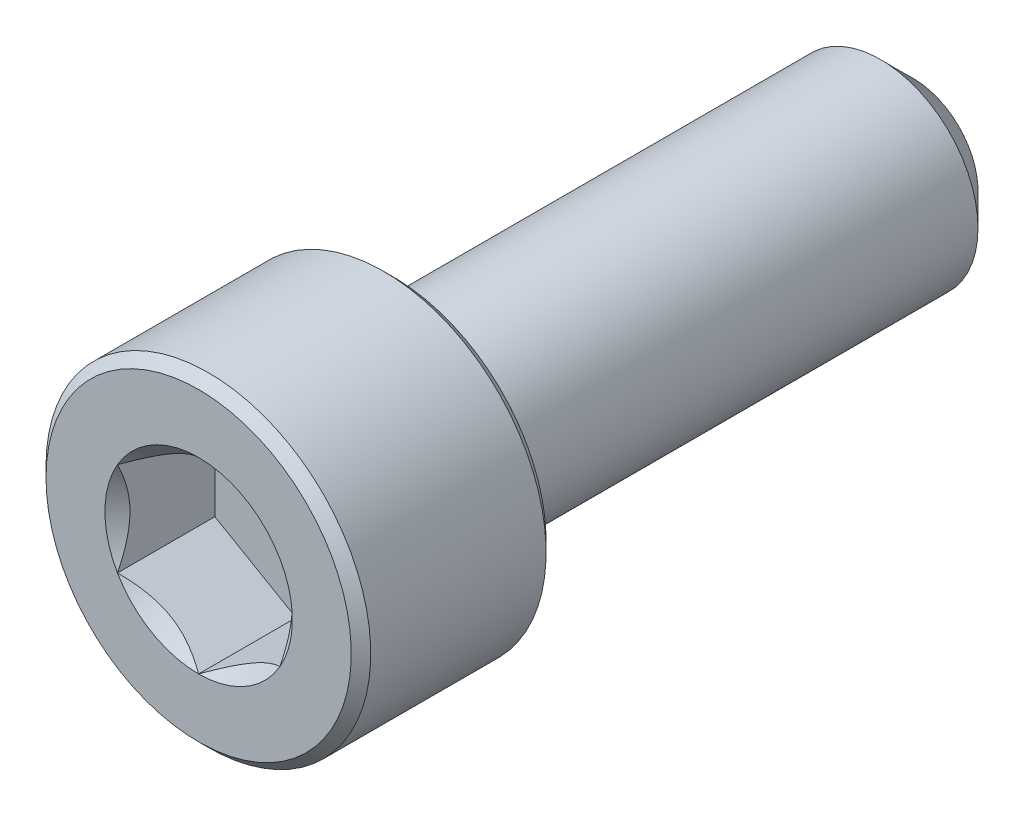
SolidWorks part; units mm, degrees
ref_plane "Front Plane" through (0, 0, 0) normal (0, 0, 1) x (1, 0, 0)
ref_plane "Top Plane" through (0, 0, 0) normal (0, 1, 0) x (1, 0, 0)
ref_plane "Right Plane" through (0, 0, 0) normal (1, 0, 0) x (0, 0, -1)
sketch "Sketch1" plane through (0, 0, 0) normal (1, 0, 0) x (0, 0, -1)
  line L0 (-11, 0) -> (11, 0) construction
  line L1 (11, 0) -> (11, 2) construction
  line L2 (11, 2) -> (10, 3) construction
  line L3 (10, 3) -> (-5, 3) construction
  line L5 (-5, 3) -> (-5, 5) construction
  line L6 (-5, 5) -> (-11, 5) construction
  line L7 (-11, 5) -> (-11, 0) construction
  line L8 (11, 2) -> (11, 3) construction
  line L9 (10.9375, 3.1083) -> (11.4375, 2.2422) construction
  line L10 (11.4375, 2.2422) -> (11.9375, 3.1083) construction
  line L11 (11.9375, 3.1083) -> (10.9375, 3.1083) construction
  line L12 (11.4375, 3.1083) -> (11.4375, 3) construction
  line L13 (11.4375, 2.2422) -> (11.4375, 2.3505) construction
  line L14 (11.375, 2.3505) -> (11.5, 2.3505) construction
  line L15 (11, 3) -> (11.875, 3) construction
  line L16 (10.9687, 3.0541) -> (11.9062, 3.0541) construction
  line L17 (11, 0) -> (11, -3) construction
  line L18 (-5.3, 5) -> (-5, 4.7) construction
  line L19 (-10.7, 5) -> (-11, 4.7) construction
  point P0 (-11, 2.5)
  point P3 (7.5, 3)
  point P4 (0, 0)
  point P22 (11.4375, 2.3505)
  point P24 (-5, 3)
  point P25 (11.4375, 3)
  point P28 (11.4375, 3.0541)
  point P29 (7.5, -3)
  point P31 (-8, 5)
  point P37 (-6.05, 5)
  point P38 (-10.55, 5)
  point P41 (-8, 0)
  dimension "head height" = 6
  dimension "D1" = 45
  dimension "Head Diameter" = 10
  dimension "Thread Size" = 6
  dimension "drive size" = 5
  dimension "Thread Pitch" = 1
  dimension "D2" = 0.125
  dimension "D3" = 1
  dimension "D4" = 3.5
  dimension "D7" = 0.3
  dimension "D8" = 0.3
  dimension "D9" = 0.3
  dimension "D10" = 0.15
  dimension "D11" = 0.75
  dimension "length" = 16
  dimension "Drive Depth" = 3
sketch "Sketch2" plane through (0, 0, 0) normal (1, 0, 0) x (0, 0, -1)
  line L1 (-10.7, 5) -> (-5.3, 5)
  line L4 (10, 3) -> (11, 2)
  line L5 (11, 2) -> (11, 0)
  line L6 (-5.3, 5) -> (-5, 4.7) construction
  line L7 (11, 0) -> (-11, 0)
  line L8 (-10.7, 5) -> (-11, 4.7) construction
  line L9 (-5.3, 5) -> (-5, 4.7)
  line L10 (-10.7, 5) -> (-11, 4.7)
  line L11 (-11, 4.7) -> (-11, 0)
  line L12 (-5, 4.7) -> (-5, 3)
  line L13 (-5, 3) -> (10, 3)
revolve "Revolve1" add sketch "Sketch2" angle 360 about L7
sketch "Sketch3" plane through (0, 0, 11) normal (0, 0, 1) x (1, 0, 0)
  line L1 (0, 2.8868) -> (-2.5, 1.4434)
  line L2 (-2.5, 1.4434) -> (-2.5, -1.4434)
  line L3 (-2.5, -1.4434) -> (0, -2.8868)
  line L4 (0, -2.8868) -> (2.5, -1.4434)
  line L5 (2.5, -1.4434) -> (2.5, 1.4434)
  line L6 (2.5, 1.4434) -> (0, 2.8868)
  circle A0 centre (0, 0) radius 2.5 construction
  dimension "D1" = 5
extrude "Cut-Extrude1" cut sketch "Sketch3" against normal up to vertex (3 mm away) up to point (0, 0, 8)
sketch "Sketch4" plane through (0, 0, 11) normal (0, 0, 1) x (1, 0, 0)
  circle A0 centre (0, 0) radius 2.8868
extrude "Cut-Extrude2" cut sketch "Sketch4" against normal blind 0.5 draft 45
ref_plane "Plane1" [suppressed] through (0, 0, 5) normal (0, 0, 1) x (1, 0, 0)
split "Split1" [suppressed] bodies to split 106
sketch "Sketch6" [suppressed] plane through (0, 0, -11) normal (0, 0, -1) x (-1, 0, 0)
  circle A0 centre (0, 0) radius 3
curve "Helix/Spiral1" [suppressed] pitch 1 height 17 turns 17
sketch "Sketch7" [suppressed] plane through (0, 0, 0) normal (1, 0, 0) x (0, 0, -1)
  line L0 (10.9687, 3.0541) -> (11.9062, 3.0541)
  line L1 (11.9062, 3.0541) -> (11.5, 2.3505)
  line L2 (11.5, 2.3505) -> (11.375, 2.3505)
  line L3 (11.375, 2.3505) -> (10.9687, 3.0541)
sweep "Cut-Sweep1" [suppressed] cut profiles "Sketch7" path "Helix/Spiral1"
sketch "Sketch8" [suppressed] plane through (0, 0, 5) normal (0, 0, -1) x (-1, 0, 0)
  circle A0 centre (0, 0) radius 3
extrude "Boss-Extrude1" [suppressed] add sketch "Sketch8" along normal through all draft 45
ref_plane "Plane2" [suppressed] through (0, 0, 8) normal (0, 0, 1) x (1, 0, 0)
sketch "Sketch9" [suppressed] plane through (0, 0, 8) normal (0, 0, 1) x (1, 0, 0)
  line L0 (0, 4.8625) -> (0.1309, 4.9983)
  line L1 (0, 4.8625) -> (-0.1309, 4.9983)
  line L2 (0, 5) -> (0, 0) construction
  line L3 (-0.1309, 4.9983) -> (0, 0) construction
  line L4 (0, 0) -> (0.1309, 4.9983) construction
  arc A0 (0.1309, 4.9983) -> (-0.1309, 4.9983) centre (0, 0) ccw
  circle A1 centre (0, 0) radius 4.8625 construction
  dimension "D2" = 9.725
  dimension "D3" = 3
extrude "Cut-Extrude4" [suppressed] cut sketch "Sketch9" against normal up to vertex and the other way up to vertex
pattern_circular "CirPattern2" [suppressed] count 96 over 360 about axis through (0, 0, 11) along (0, 0, -1) of bodies 113
equation "\"D2@Sketch1\" = \"Thread Pitch@Sketch1\" / 8"
equation "\"D3@Sketch1\" = \"Thread Pitch@Sketch1\""
equation "\"D3@Helix/Spiral1\" = \"length@Sketch1\" + \"Thread Pitch@Sketch1\""
equation "\"D4@Helix/Spiral1\" = \"Thread Pitch@Sketch1\""
equation "\"D4@Sketch1\" = \"Thread Pitch@Sketch1\" * 3.5"
equation "\"D7@Sketch1\"=\"head height@Sketch1\"*.05"
equation "\"D8@Sketch1\"=\"D7@Sketch1\""
equation "\"D9@Sketch1\"=\"D7@Sketch1\""
equation "\"D10@Sketch1\"=\"D7@Sketch1\"/2"
equation "\"D11@Sketch1\"=\"D10@Sketch1\"*5"
equation "\"D1@CirPattern2\"=( 360 / \"D3@Sketch9\" )*0.8"
equation "\"D1@Sketch3\" = \"drive size@Sketch1\""
equation "\"D2@Sketch9\"=\"Head Diameter@Sketch1\" * 0.9725"
